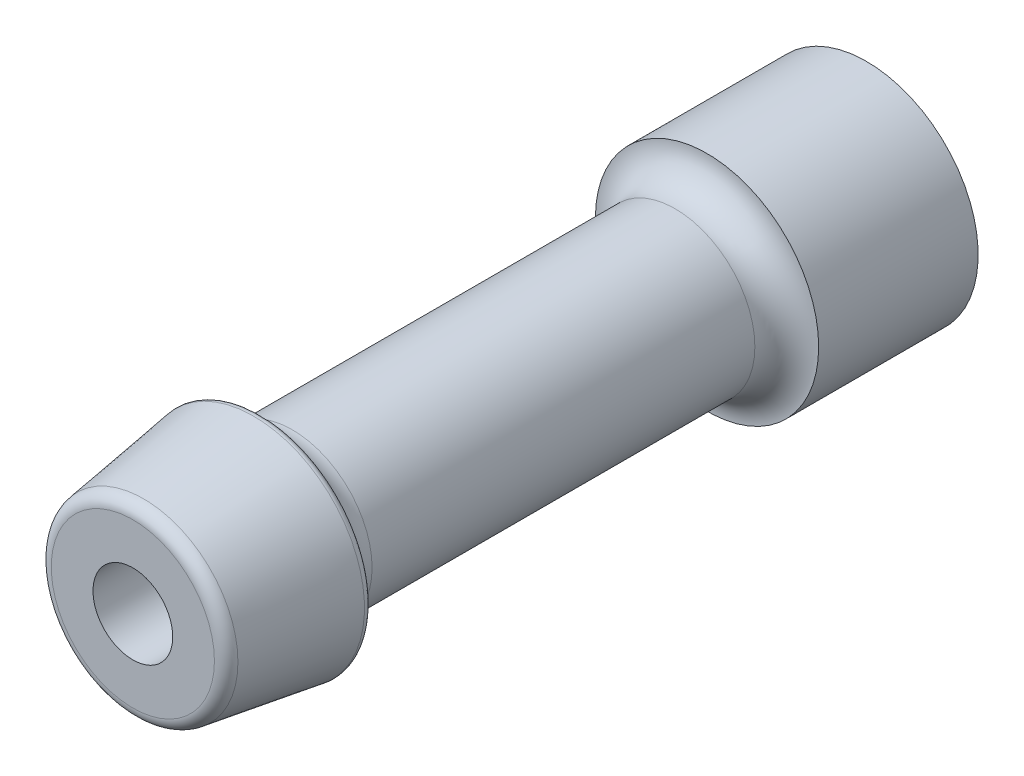
SolidWorks part; units mm, degrees
material "Custom Plastic"
ref_plane "X-Y Datum" through (0, 0, 0) normal (0, 0, 1) x (1, 0, 0)
ref_plane "X-Z Datum" through (0, 0, 0) normal (0, 1, 0) x (1, 0, 0)
ref_plane "Y-Z Datum" through (0, 0, 0) normal (1, 0, 0) x (0, 0, -1)
sketch "Sketch1" plane through (0, 0, 0) normal (0, 0, 1) x (1, 0, 0)
  circle A0 centre (0, 0) radius 4.445
  dimension "D1" = 8.89
extrude "Boss-Extrude1" add sketch "Sketch1" along normal blind 29.21
sketch3d "3DSketch1"
  line L0 (0, 0, 29.21) -> (0, 0, 0)
  line L1 (0, 0, 29.21) -> (0, 0, 0) construction
sketch "Sketch2" plane through (0, 0, 29.21) normal (0, 0, 1) x (1, 0, 0)
  circle A0 centre (0, 0) radius 1.5875
  dimension "D1" = 3.175
sweep "Cut-Sweep1" cut profiles "Sketch2" path "3DSketch1"
sketch "Sketch3" plane through (0, 0, 29.21) normal (0, 0, 1) x (1, 0, 0)
  circle A0 centre (0, 0) radius 3.175
  circle A1 centre (0, 0) radius 6.35
  dimension "D1" = 12.7
  dimension "D2" = 6.35
extrude "Cut-Extrude1" cut sketch "Sketch3" against normal blind 17.78 from offset 5.08 offset against normal yes
fillet "Fillet1" radius 1.27 1 edges at (3.175, 0, 6.35)
fillet "Fillet2" radius 1.27 1 edges at (3.175, 0, 24.13)
chamfer "Chamfer1" distance 5.08 angle 8.5 1 edges at (4.445, 0, 29.21) first distance on face at (4.445, 0, 24.13)
fillet "Fillet3" radius 0.254 1 edges at (4.445, 0, 24.13)
fillet "Fillet4" radius 0.508 1 edges at (3.6858, 0, 29.21)
